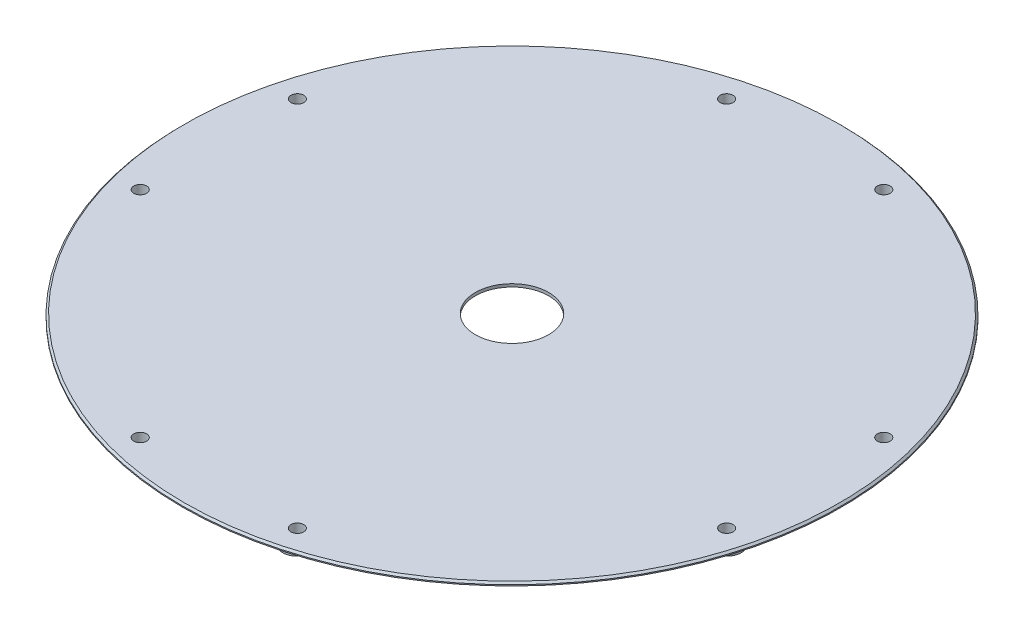
SolidWorks part; units mm, degrees
ref_plane "Ebene vorne" through (0, 0, 0) normal (0, 0, 1) x (1, 0, 0)
ref_plane "Ebene oben" through (0, 0, 0) normal (0, 1, 0) x (1, 0, 0)
ref_plane "Ebene rechts" through (0, 0, 0) normal (1, 0, 0) x (0, 0, -1)
sketch "Skizze1" plane through (0, 0, 0) normal (0, 1, 0) x (1, 0, 0)
  circle A0 centre (0, 0) radius 90
  dimension "D1" = 180
extrude "Aufsatz-Linear austragen1" add sketch "Skizze1" along normal blind 0.8
sketch "Skizze2" plane through (0, 0, 0) normal (0, -1, 0) x (1, 0, 0)
  line L0 (0, 0) -> (0, 90) construction
  line L1 (15, 30) -> (15, 88.7412) construction
  line L2 (-15, 30) -> (-15, 88.7412) construction
  line L3 (-15, 30) -> (-15, 40)
  line L4 (-15, 30) -> (-21, 30)
  line L5 (-15, 40) -> (-21, 40)
  line L6 (-21, 30) -> (-21, 40)
  line L7 (15, 30) -> (15, 40)
  line L8 (15, 30) -> (21, 30)
  line L9 (15, 40) -> (21, 40)
  line L10 (21, 30) -> (21, 40)
  circle A0 centre (0, 0) radius 90 construction
  dimension "D1" = 15
  dimension "D2" = 60
  dimension "D3" = 10
  dimension "D4" = 6
extrude "Aufsatz-Linear austragen2" add sketch "Skizze2" along normal blind 14
chamfer "Fase1" distance 14 angle 45 2 edges at (18, 0, 40) (-18, 0, 40)
sketch "Skizze3" plane through (21, 0, 0) normal (1, 0, 0) x (0, 0, -1)
  line L0 (-40, -14) -> (-40, 0) construction
  line L2 (-40, 0) -> (-30, -14) construction
  line L3 (-90, 0) -> (90, 0) construction
  circle A0 centre (-35, -7) radius 2.15
  dimension "D1" = 4.3
extrude "Schnitt-Linear austragen1" cut sketch "Skizze3" against normal blind 42
pattern_circular "Kreismuster1" count 3 over 360 about axis through (0, 0.8, 0) along (0, -1, 0) of "Aufsatz-Linear austragen2", "Fase1", "Schnitt-Linear austragen1"
sketch "Skizze4" plane through (0, 0, 0) normal (0, -1, 0) x (1, 0, 0)
  line L0 (-15, 54) -> (-15, 78.5812)
  line L1 (15, 54) -> (15, 78.5812)
  line L2 (54.2654, -14.0096) -> (75.5533, -26.3002)
  line L3 (39.2654, -39.9904) -> (60.5533, -52.281)
  line L4 (-39.2654, -39.9904) -> (-60.5533, -52.281)
  line L5 (-54.2654, -14.0096) -> (-75.5533, -26.3002)
  circle A0 centre (0, 0) radius 33.541
  circle A1 centre (0, 0) radius 80
  circle A2 centre (0, 0) radius 90 construction
  circle A3 centre (0, 0) radius 74
  circle A4 centre (0, 0) radius 36.6197
  point P28 (0, 0)
  line M6 (33.4808, -2.0096) -> (36.4808, 3.1865)
  line M10 (-18.4808, -27.9904) -> (-15.4808, -33.1865)
  line M14 (-15, 30) -> (-21, 30)
  line M19 (21, 30) -> (15, 30)
  line M23 (-36.4808, 3.1865) -> (-33.4808, -2.0096)
  line M27 (15.4808, -33.1865) -> (18.4808, -27.9904)
  dimension "D1" = 10
  dimension "D2" = 6
  dimension "D3" = 3
extrude "Aufsatz-Linear austragen3" add sketch "Skizze4" along normal blind 3 contours A3 L0 A1 L5 | A3 L2 A1 L1 | A3 L4 A1 L3 | A4 A0 M10 M27 | A4 A0 M14 M23 | A4 A0 M6 M19 region at (-65.1545, 0, 37.617) region at (16.2339, 0, 75.5225) region at (0, 0, -75.2496) region at (29.0481, 0, 16.7709) region at (-29.0481, 0, 16.7709) region at (0, 0, -33.5418)
sketch "Skizze6" plane through (0, 0, 0) normal (0, -1, 0) x (1, 0, 0)
  line L0 (0, 0) -> (0, -90) construction
  line L1 (0, 0) -> (-20.7055, -77.2741) construction
  line L2 (-13.2849, -34.125) -> (-27.1344, -85.8121) construction
  line L3 (-5.5575, -36.1955) -> (-19.407, -87.8827) construction
  line L4 (-3.8637, 1.0353) -> (-27.1574, -85.898) construction
  line L5 (3.8637, -1.0353) -> (-19.43, -87.9686) construction
  line L6 (-24.5433, -76.1421) -> (-25.3198, -79.0399)
  line L7 (-16.8159, -78.2127) -> (-17.5924, -81.1105)
  line L8 (-17.5924, -81.1105) -> (-25.3198, -79.0399) construction
  line L9 (0, 0) -> (-23.2937, -86.9333) construction
  line L10 (-24.5433, -76.1421) -> (-16.8159, -78.2127)
  line L11 (17.5924, -81.1105) -> (25.3198, -79.0399) construction
  line L12 (0, 0) -> (20.7055, -77.2741) construction
  line L13 (5.5575, -36.1955) -> (19.407, -87.8827) construction
  line L14 (13.2849, -34.125) -> (27.1344, -85.8121) construction
  line L15 (24.5433, -76.1421) -> (16.8159, -78.2127)
  line L16 (16.8159, -78.2127) -> (17.5924, -81.1105)
  line L17 (24.5433, -76.1421) -> (25.3198, -79.0399)
  circle A0 centre (0, 0) radius 90 construction
  arc A1 (-15.4808, -33.1865) -> (15.4808, -33.1865) centre (0, 0) ccw construction
  arc A4 (-60.5533, -52.281) -> (60.5533, -52.281) centre (0, 0) ccw construction
  arc A5 (-17.5924, -81.1105) -> (-25.3198, -79.0399) centre (-21.4561, -80.0752) cw
  arc A6 (17.5924, -81.1105) -> (25.3198, -79.0399) centre (21.4561, -80.0752) ccw
  dimension "D1" = 15
  dimension "D4" = 3
  dimension "D2" = 4
  dimension "D3" = 4
extrude "Aufsatz-Linear austragen4" add sketch "Skizze6" along normal up to surface (3 mm away) up to face at (0, -3, -63.8758)
sketch "Skizze7" plane through (0, -3, 0) normal (0, -1, 0) x (1, 0, 0)
  line L0 (-25.3198, -79.0399) -> (-17.5924, -81.1105) construction
  line L1 (17.5924, -81.1105) -> (25.3198, -79.0399) construction
  line L2 (25.3198, -79.0399) -> (24.5433, -76.1421) construction
  circle A0 centre (-21.4561, -80.0752) radius 1.75
  circle A1 centre (21.4561, -80.0752) radius 1.75
  arc A2 (17.5924, -81.1105) -> (25.3198, -79.0399) centre (21.4561, -80.0752) ccw construction
  dimension "D1" = 3.5
extrude "Schnitt-Linear austragen2" cut sketch "Skizze7" against normal up to next
pattern_circular "Kreismuster2" count 4 over 360 about axis through (0, -3, 0) along (0, 1, 0) of "Aufsatz-Linear austragen4", "Schnitt-Linear austragen2"
sketch "Skizze8" plane through (0, 0.8, 0) normal (0, 1, 0) x (1, 0, 0)
  circle A0 centre (0, 0) radius 10
  dimension "D1" = 20
extrude "Schnitt-Linear austragen3" cut sketch "Skizze8" against normal up to next
chamfer "Fase2" distance 0.5 angle 45 1 edges at (0, 0.8, 90)
